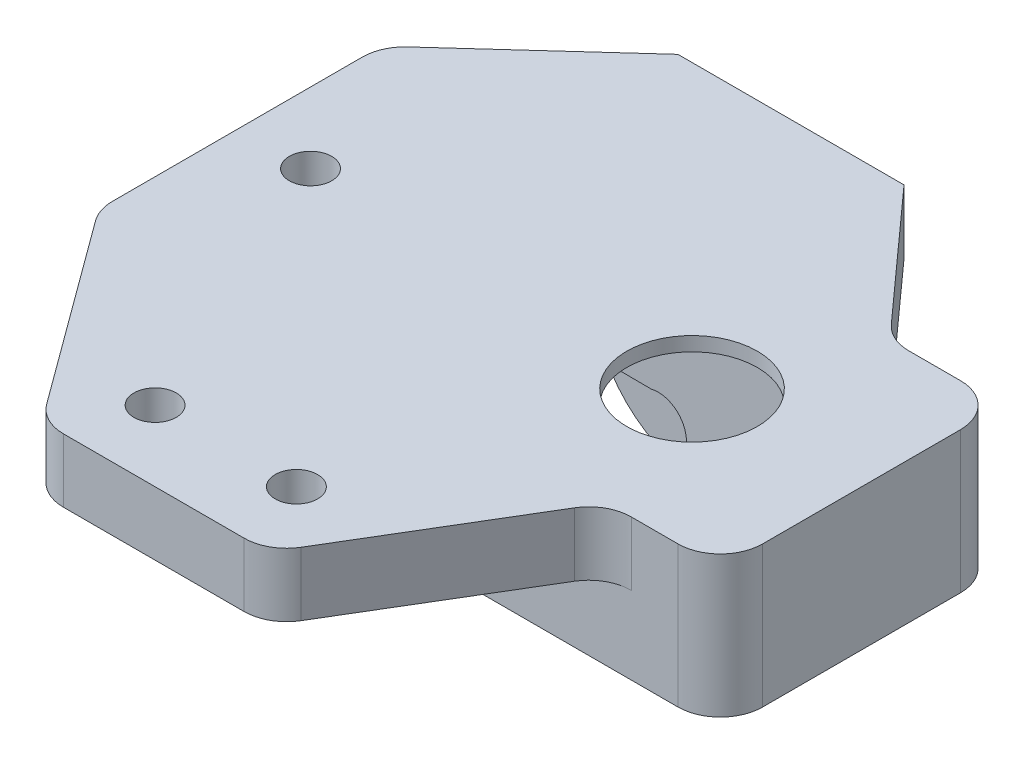
SolidWorks part; units mm, degrees
ref_plane "Front Plane" through (0, 0, 0) normal (0, 0, 1) x (1, 0, 0)
ref_plane "Top Plane" through (0, 0, 0) normal (0, 1, 0) x (1, 0, 0)
ref_plane "Right Plane" through (0, 0, 0) normal (1, 0, 0) x (0, 0, -1)
sketch "Sketch1" plane through (0, 0, 0) normal (0, 1, 0) x (1, 0, 0)
  line L0 (0, 0) -> (16, 0)
  line L1 (16, 0) -> (25, 15)
  line L2 (25, 15) -> (33, 15)
  line L3 (33, 15) -> (33, 35)
  line L4 (33, 35) -> (25, 35)
  line L5 (25, 35) -> (16, 45)
  line L6 (16, 45) -> (0, 45)
  line L7 (0, 45) -> (-11, 35)
  line L8 (-11, 35) -> (-11, 15)
  line L9 (-11, 15) -> (0, 0)
  dimension "D1" = 44
  dimension "D2" = 10
  dimension "D3" = 20
  dimension "D4" = 8
  dimension "D5" = 8
  dimension "D6" = 16
  dimension "D7" = 16
  dimension "D8" = 20
  dimension "D9" = 15
  dimension "D10" = 10
  dimension "D11" = 17
  dimension "D12" = 17
extrude "Boss-Extrude1" add sketch "Sketch1" along normal blind 4.5
sketch "Sketch2" plane through (0, 0, 0) normal (0, -1, 0) x (-1, 0, 0)
  line L1 (-33, 15) -> (1, 15)
  line L2 (-33, 15) -> (-33, 35)
  line L3 (-33, 35) -> (1, 35)
  line L4 (1, 15) -> (1, 35)
  dimension "D1" = 20
  dimension "D2" = 34
extrude "Boss-Extrude2" add sketch "Sketch2" along normal blind 5.5
sketch "Sketch3" plane through (0, -5.5, 0) normal (0, -1, 0) x (-1, 0, 0)
  line L0 (-33, 35) -> (-33, 15) construction
  circle A0 centre (-21, 25) radius 4.6217
  dimension "D1" = 25
  dimension "D2" = 12
extrude "Cut-Extrude1" cut sketch "Sketch3" against normal blind 15.5
sketch "Sketch4" plane through (0, -5.5, 0) normal (0, -1, 0) x (1, 0, 0)
  line L1 (4.6, -18.5) -> (27, -18.5)
  line L2 (4.6, -18.5) -> (4.6, -31.1)
  line L3 (4.6, -31.1) -> (27, -31.1)
  line L4 (27, -18.5) -> (27, -31.1)
  dimension "D1" = 22.4
  dimension "D2" = 12.6
  dimension "D3" = 18.5
  dimension "D4" = 4.6
extrude "Cut-Extrude2" cut sketch "Sketch4" against normal blind 9
sketch "Sketch5" plane through (0, 0, 0) normal (0, -1, 0) x (-1, 0, 0)
  circle A0 centre (-3, 5) radius 1.5
  circle A1 centre (-13, 5) radius 1.5
  dimension "D2" = 3
  dimension "D3" = 3
  dimension "D1" = 10
  dimension "D4" = 5
  dimension "D5" = 5
  dimension "D6" = 3
extrude "Cut-Extrude3" cut sketch "Sketch5" against normal blind 9
sketch "Sketch6" plane through (0, -5.5, 0) normal (0, -1, 0) x (-1, 0, 0)
  circle A0 centre (-2, 25) radius 1
  circle A1 centre (-30, 25) radius 1
  dimension "D3" = 2
  dimension "D4" = 2
  dimension "D1" = 25
  dimension "D2" = 25
  dimension "D5" = 30
  dimension "D6" = 2
extrude "Cut-Extrude4" cut sketch "Sketch6" against normal blind 9
sketch "Sketch7" plane through (0, 0, 0) normal (0, -1, 0) x (-1, 0, 0)
  circle A0 centre (6, 25) radius 1.5
  circle A1 centre (-21, 25) radius 4.6217 construction
  dimension "D1" = 3
  dimension "D2" = 27
  dimension "D3" = 25
extrude "Cut-Extrude5" cut sketch "Sketch7" against normal blind 19
sketch "Sketch8" plane through (0, 0, 0) normal (0, -1, 0) x (-1, 0, 0)
  line L1 (0, 44) -> (-16, 44)
  line L2 (0, 44) -> (0, 39)
  line L3 (0, 39) -> (-16, 39)
  line L4 (-16, 44) -> (-16, 39)
  dimension "D1" = 5
  dimension "D2" = 16
  dimension "D3" = 39
extrude "Boss-Extrude3" add sketch "Sketch8" along normal blind 15
sketch "Sketch9" plane through (0, 0, -45) normal (0, 0, -1) x (-1, 0, 0)
  circle A1 centre (-12.5, -5) radius 0.75
  circle A2 centre (-3.5, -5) radius 0.75
  dimension "D6" = 1.5
  dimension "D7" = 1.5
  dimension "D1" = 9
  dimension "D2" = 3.5
extrude "Cut-Extrude6" cut sketch "Sketch9" against normal blind 6
sketch "Sketch10" plane through (0, 0, -45) normal (0, 0, -1) x (-1, 0, 0)
  circle A0 centre (-8, -5) radius 2
  dimension "D3" = 4
  dimension "D1" = 8
  dimension "D2" = 5
extrude "Cut-Extrude7" cut sketch "Sketch10" against normal blind 36
fillet "Fillet1" radius 3 10 edges at (-11, 2.25, -35) (25, 2.25, -35) (33, -0.5, -35) (33, -0.5, -15) (25, 2.25, -15) (-11, 2.25, -15) (16, 2.25, 0) (0, 2.25, 0) (-1, -2.75, -35) (-1, -2.75, -15)
fillet "Fillet2" radius 8 2 edges at (16, -15, -41.5) (0, -15, -41.5)
fillet "Fillet3" radius 2 1 edges at (8, 0, -39)
sketch "Sketch11" plane through (0, 0, -39) normal (0, 0, 1) x (1, 0, 0)
  line L0 (3.5, -3) -> (12.0149, -3.0597)
  line L1 (3.5, -7) -> (12.0149, -6.9403)
  arc A0 (12.0149, -6.9403) -> (12.0149, -3.0597) centre (12.5, -5) ccw
  arc A1 (3.5, -3) -> (3.5, -7) centre (3.5, -5) ccw
  dimension "D1" = 4
  dimension "D2" = 4
extrude "Cut-Extrude8" cut sketch "Sketch11" along normal blind 30
